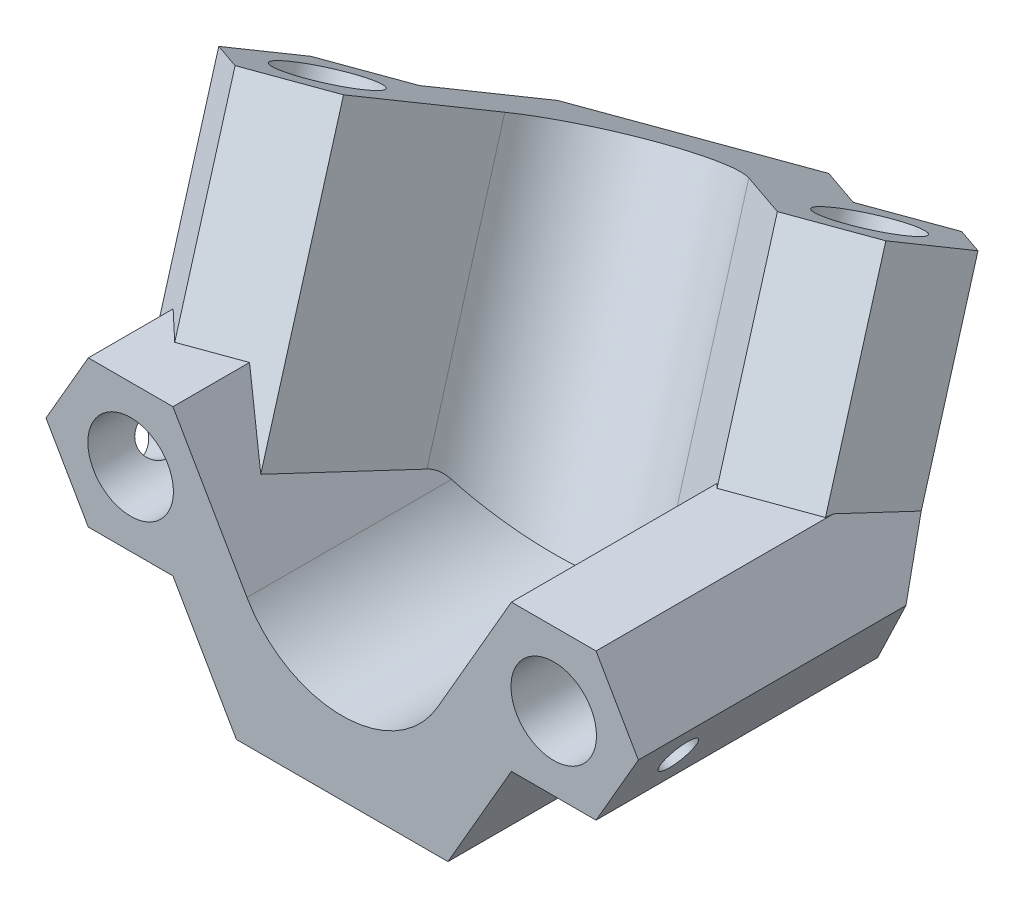
SolidWorks part; units mm, degrees
ref_plane "Front Plane" through (0, 0, 0) normal (0, 0, 1) x (1, 0, 0)
ref_plane "Top Plane" through (0, 0, 0) normal (0, 1, 0) x (1, 0, 0)
ref_plane "Right Plane" through (0, 0, 0) normal (1, 0, 0) x (0, 0, -1)
sketch "Sketch1" plane through (0, 0, 0) normal (0, 1, 0) x (1, 0, 0)
  line L0 (0, 0) -> (0, -10) construction
  line L1 (0, 0) -> (-3.4202, 9.3969) construction
  dimension "D1" = 10
  dimension "D2" = 160
  dimension "D3" = 10
ref_plane "Plane1" through (0, 0, 0) normal (0.9397, 0, -0.342) x (-0.342, 0, -0.9397)
sketch "Sketch2" plane through (0, 0, 0) normal (0.9397, 0, -0.342) x (-0.342, 0, -0.9397)
  line L0 (0, 0) -> (10, 0) construction
  line L1 (0, 0) -> (10, 0) construction
  line L2 (10, 0) -> (10, 17.3205) construction
  line L3 (10, 17.3205) -> (0, 0) construction
  dimension "D1" = 60
  dimension "D2" = 10
sketch "Sketch3" plane through (0, 0, 0) normal (0, 0, 1) x (1, 0, 0)
  line L0 (0, 15) -> (0, -15) construction
  line L1 (13.8564, 6) -> (8.6603, 15) construction
  line L2 (8.6603, 15) -> (0, 15) construction
  line L3 (-8.6603, 15) -> (-13.8564, 6) construction
  line L4 (-13.8564, -6) -> (-8.6603, -15)
  line L5 (-8.6603, -15) -> (8.6603, -15)
  line L6 (8.6603, -15) -> (13.8564, -6)
  line L7 (0, 0) -> (17.3205, 0) construction
  line L8 (13.8564, 6) -> (12.1244, 3) construction
  line L9 (24.2487, 0) -> (20.7846, 6)
  line L10 (20.7846, 6) -> (13.8564, 6)
  line L11 (12.1244, 3) -> (7.7942, -4.5) construction
  line L12 (12.1244, -3) -> (13.8564, -6) construction
  line L13 (13.8564, -6) -> (20.7846, -6)
  line L14 (20.7846, -6) -> (24.2487, 0)
  line L15 (10.3923, 0) -> (12.1244, -3) construction
  line L16 (13.8564, -6) -> (14.3205, -5.1962) construction
  line L17 (15.5705, -3.0311) -> (17.3205, 0) construction
  line L18 (14.3205, -5.1962) -> (15.5705, -3.0311) construction
  line L19 (17.3205, 0) -> (15.5705, 3.0311) construction
  line L20 (15.5705, 3.0311) -> (14.3205, 5.1962) construction
  line L21 (14.3205, 5.1962) -> (13.8564, 6) construction
  line L22 (-13.8564, -6) -> (-20.7846, -6)
  line L23 (-20.7846, -6) -> (-24.2487, 0)
  line L24 (-24.2487, 0) -> (-20.7846, 6)
  line L25 (-20.7846, 6) -> (-13.8564, 6)
  line L26 (-13.8564, 6) -> (-15.5705, 3.0311) construction
  line L27 (-15.5705, 3.0311) -> (-17.3205, 0) construction
  line L28 (-17.3205, 0) -> (-15.5705, -3.0311) construction
  line L29 (-15.5705, -3.0311) -> (-13.8564, -6) construction
  line L30 (-17.3205, 6) -> (-17.3205, -6) construction
  line L31 (-7.7942, -4.5) -> (-13.8564, 6)
  line L32 (7.7942, -4.5) -> (13.8564, 6)
  line L33 (-10.3923, 0) -> (-7.7942, -4.5) construction
  line L34 (0, 15) -> (-8.6603, 15) construction
  line L35 (7.7942, -4.5) -> (10.3923, 0) construction
  line L36 (10.3923, 0) -> (7.7942, -4.5) construction
  circle A0 centre (0, 0) radius 15 construction
  circle A1 centre (17.3205, 0) radius 3.5
  circle A2 centre (17.3205, 0) radius 6 construction
  circle A3 centre (-17.3205, 0) radius 3.5
  arc A4 (-7.7942, -4.5) -> (7.7942, -4.5) centre (0, 0) ccw
  arc A5 (0, 9) -> (-7.7942, -4.5) centre (0, 0) ccw construction
  arc A6 (7.7942, -4.5) -> (0, 9) centre (0, 0) ccw construction
  dimension "D2" = 7
  dimension "D4" = 18
  dimension "D1" = 30
  dimension "D3" = 12
extrude "Boss-Extrude1" add sketch "Sketch3" along normal blind 15
ref_plane "Plane2" through (-3.4202, 17.3205, -9.3969) normal (0.171, -0.866, 0.4698) x (-0.9849, -0.1641, 0.056)
sketch "Sketch25" plane through (0, 0, 0) normal (0, 0, -1) x (-1, 0, 0)
  line L0 (-7.7942, -4.5) -> (-13.8564, 6)
  line L1 (-13.8564, 6) -> (-20.7846, 6)
  line L2 (-20.7846, 6) -> (-24.2487, 0)
  line L3 (-24.2487, 0) -> (-20.7846, -6)
  line L4 (-20.7846, -6) -> (-13.8564, -6)
  line L5 (-13.8564, -6) -> (-8.6603, -15)
  line L6 (-8.6603, -15) -> (8.6603, -15)
  line L7 (8.6603, -15) -> (13.8564, -6)
  line L8 (13.8564, -6) -> (20.7846, -6)
  line L9 (20.7846, -6) -> (24.2487, 0)
  line L10 (24.2487, 0) -> (20.7846, 6)
  line L11 (20.7846, 6) -> (13.8564, 6)
  line L12 (13.8564, 6) -> (7.7942, -4.5)
  arc A0 (-7.7942, -4.5) -> (7.7942, -4.5) centre (0, 0) ccw
  arc A1 (-7.7942, -4.5) -> (7.7942, -4.5) centre (0, 0) ccw construction
  arc A2 (7.7942, -4.5) -> (-7.7942, -4.5) centre (0, 0) ccw construction
sketch "Sketch11" plane through (-3.4202, 17.3205, -9.3969) normal (0.171, -0.866, 0.4698) x (-0.9849, -0.1641, 0.056)
  line L0 (-4.9224, -14.1693) -> (4.9224, 14.1693) construction
  line L7 (13.1031, 11.3274) -> (-3.2583, 17.0113)
  line L20 (-3.2583, 17.0113) -> (-11.1201, 10.2148)
  line L21 (-15.058, -1.1206) -> (-13.1031, -11.3274) construction
  line L22 (-4.9224, -14.1693) -> (3.2583, -17.0113) construction
  line L23 (3.2583, -17.0113) -> (11.1201, -10.2148) construction
  line L24 (16.3613, -5.6839) -> (15.7029, -2.2464) construction
  line L25 (2.8419, 8.1807) -> (0, 0) construction
  line L26 (-16.3613, 5.6839) -> (16.3613, -5.6839) construction
  line L27 (15.058, 1.1206) -> (12.4374, -1.1449) construction
  line L28 (-11.1201, 10.2148) -> (-17.6647, 12.4884)
  line L35 (-17.6647, 12.4884) -> (-22.9059, 7.9574)
  line L42 (-22.9059, 7.9574) -> (-21.6026, 1.1529)
  line L43 (-21.6026, 1.1529) -> (-15.058, -1.1206)
  line L44 (-15.058, -1.1206) -> (-5.8859, 6.8085)
  line L45 (-8.8393, -1.6931) -> (-10.4685, 6.8126) construction
  line L46 (22.9059, -7.9574) -> (21.6026, -1.1529)
  line L47 (21.6026, -1.1529) -> (15.058, 1.1206)
  line L48 (5.8859, -6.8085) -> (9.8168, -3.4103) construction
  line L49 (8.8393, 1.6931) -> (11.1201, -10.2148)
  line L50 (11.1201, -10.2148) -> (17.6647, -12.4884)
  line L51 (17.6647, -12.4884) -> (22.9059, -7.9574)
  line L52 (12.4374, -1.1449) -> (5.8859, -6.8085) construction
  line L53 (9.8168, -3.4103) -> (8.8393, 1.6931) construction
  line L54 (15.2326, 0.209) -> (15.058, 1.1206) construction
  line L55 (15.058, 1.1206) -> (13.1031, 11.3274)
  line L56 (15.7029, -2.2464) -> (15.2326, 0.209) construction
  line L57 (13.7136, -7.9728) -> (16.3613, -5.6839) construction
  line L58 (11.8223, -9.6078) -> (13.7136, -7.9728) construction
  line L59 (11.1201, -10.2148) -> (11.8223, -9.6078) construction
  line L60 (-10.4685, 6.8126) -> (-11.1201, 10.2148) construction
  line L61 (-11.8223, 9.6078) -> (-13.7136, 7.9728) construction
  line L62 (-13.7136, 7.9728) -> (-16.3613, 5.6839) construction
  line L63 (-16.3613, 5.6839) -> (-15.7029, 2.2464) construction
  line L64 (-11.1201, 10.2148) -> (-11.8223, 9.6078) construction
  line L65 (-15.7029, 2.2464) -> (-15.2326, -0.209) construction
  line L66 (-15.2326, -0.209) -> (-15.058, -1.1206) construction
  line L67 (-5.8859, 6.8085) -> (-9.8168, 3.4103) construction
  line L68 (-9.8168, 3.4103) -> (-8.8393, -1.6931) construction
  line L69 (-13.1031, -11.3274) -> (-4.9224, -14.1693) construction
  circle A0 centre (0, 0) radius 15 construction
  circle A2 centre (-16.3613, 5.6839) radius 6 construction
  circle A4 centre (-16.3613, 5.6839) radius 3.5
  circle A5 centre (16.3613, -5.6839) radius 6 construction
  circle A6 centre (16.3613, -5.6839) radius 3.5
  arc A7 (8.8393, 1.6931) -> (-5.8859, 6.8085) centre (0, 0) ccw
  arc A8 (-2.9534, -8.5016) -> (8.8393, 1.6931) centre (0, 0) ccw construction
  arc A9 (-5.8859, 6.8085) -> (-2.9534, -8.5016) centre (0, 0) ccw construction
  dimension "D2" = 12
  dimension "D4" = 12
  dimension "D3" = 7
  dimension "D5" = 7
  dimension "D6" = 18
  dimension "D1" = 30
extrude "Boss-Extrude6" add sketch "Sketch11" along normal up to surface (33.8564 mm away) up to face at (0, -15, 7.5)
sketch "Sketch22" plane through (0, 0, 15) normal (0, 0, 1) x (1, 0, 0)
  line L0 (8.6603, -15) -> (-7.1843, -15)
  line L1 (-9.2861, -6.9129) -> (-7.1843, -15) construction
  circle A0 centre (-17.3205, 0) radius 3.5
  arc A1 (-15.7099, -3.1074) -> (-17.8449, 3.4605) centre (-17.3205, 0) ccw construction
  circle A2 centre (17.3205, 0) radius 3.5
  circle A3 centre (17.3205, 0) radius 3.5 construction
  circle A4 centre (0, 0) radius 9
  arc A5 (-7.7942, -4.5) -> (7.7942, -4.5) centre (0, 0) ccw construction
  point P18 (0, 0)
  point P20 (-7.1843, -15)
  arc M23 (7.7942, -4.5) -> (-7.7942, -4.5) centre (0, 0) cw
extrude "Cut-Extrude5" cut sketch "Sketch22" against normal up to surface (15 mm away) contours A4 M23 | A0 | A2 region at (0, 0, 15) up to face at (-19.4628, -1.9467, 0)
sketch "Sketch23" plane through (0, 0, 0) normal (0, 1, 0) x (1, 0, 0)
  line L0 (24.2487, -15) -> (24.2487, 0) construction
  line L1 (-24.2487, -15) -> (24.2487, -15)
  line L2 (-24.2487, -15) -> (-24.2487, -21.7571)
  line L3 (-24.2487, -21.7571) -> (24.2487, -21.7571)
  line L4 (24.2487, -15) -> (24.2487, -21.7571)
extrude "Cut-Extrude6" cut sketch "Sketch23" against normal through all both and the other way through all
sketch "Sketch24" plane through (0, 0, 15) normal (0, 0, 1) x (1, 0, 0)
  line L0 (-24.2487, 0) -> (-20.7846, -6)
  line L1 (-20.7846, -6) -> (-13.8564, -6)
  line L2 (-13.8564, -6) -> (-8.6603, -15)
  line L3 (-8.6603, -15) -> (-19.6596, -15)
  line L4 (-19.6596, -15) -> (-24.2487, 0)
  line L5 (8.6603, -15) -> (13.8564, -6)
  line L6 (13.8564, -6) -> (20.7846, -6)
  line L7 (20.7846, -6) -> (24.2487, 0)
  line L8 (24.2487, 0) -> (25.7483, -15)
  line L9 (25.7483, -15) -> (8.6603, -15)
  point P14 (0, 0)
extrude "Cut-Extrude7" cut sketch "Sketch24" against normal through all both and the other way through all
extrude "Boss-Extrude7" add sketch "Sketch25" along normal up to surface (18.5042 mm away) up to face at (-6.3157, -3.7874, -13.8064)
sketch "Sketch26" plane through (-3.4202, 17.3205, -9.3969) normal (-0.171, 0.866, -0.4698) x (0.9853, 0.1503, -0.0815)
  line L0 (-12.769, 11.7026) -> (-15.0192, 1.5568)
  line L1 (-15.0192, 1.5568) -> (-24.01, -1.2771)
  line L2 (-25.1148, -13.1846) -> (-23.1081, 8.4437) construction
  line L3 (-24.01, -1.2771) -> (-23.1081, 8.4437)
  line L4 (-23.1081, 8.4437) -> (-12.769, 11.7026)
  line L5 (3.7502, 16.9096) -> (11.4117, 9.8881)
  line L6 (11.4117, 9.8881) -> (18.0194, 11.9709)
  line L7 (18.0194, 11.9709) -> (24.4549, 6.0728)
  line L8 (22.6683, -13.1846) -> (26.1144, 23.959) construction
  line L9 (24.4549, 6.0728) -> (26.1144, 23.959)
  line L10 (26.1144, 23.959) -> (3.7502, 16.9096)
extrude "Cut-Extrude8" cut sketch "Sketch26" against normal through all both and the other way through all
sketch "Sketch27" plane through (-18.1865, -10.5, 0) normal (-0.866, -0.5, 0) x (0, 0, 1)
  line L0 (15, 8.6603) -> (2.6658, 8.6603) construction
  line L1 (15, 12.1244) -> (15, 5.1962) construction
  line L2 (1.453, 12.1244) -> (3.8786, 5.1962) construction
  line L3 (10, 12.1244) -> (10, 5.1962) construction
  line L4 (15, 12.1244) -> (1.453, 12.1244) construction
  line L5 (15, 5.1962) -> (3.8786, 5.1962) construction
  circle A0 centre (10, 8.6603) radius 1.5
  dimension "D1" = 3
  dimension "D2" = 5
extrude "Cut-Extrude9" cut sketch "Sketch27" against normal up to surface and the other way through all up to face at (-17.3205, 0, 0.7154)
sketch "Sketch28" plane through (18.1865, -10.5, 0) normal (0.866, -0.5, 0) x (0, 0, -1)
  line L0 (-15, 8.6603) -> (7.4822, 8.6603) construction
  line L1 (-15, 5.1962) -> (-15, 12.1244) construction
  line L2 (8.0554, 5.1962) -> (6.909, 12.1244) construction
  circle A0 centre (-10, 8.6603) radius 1.5
  dimension "D1" = 3
  dimension "D2" = 5
extrude "Cut-Extrude10" cut sketch "Sketch28" against normal up to surface (2.8377 mm away) up to face at (20.8205, 0, 0)
sketch "Sketch29" plane through (-20.1998, -5.25, -2.3247) normal (-0.9619, -0.25, -0.1107) x (-0.1071, -0.0278, 0.9939)
  line L0 (-1.8237, 21.7181) -> (5.4703, 8.1224) construction
  line L1 (1.2289, 23.3557) -> (-4.8762, 20.0804) construction
  line L2 (1.2869, 8.5925) -> (9.6536, 7.6523) construction
  circle A0 centre (0.5401, 17.3121) radius 1.5
  dimension "D1" = 3
  dimension "D2" = 5
extrude "Cut-Extrude11" cut sketch "Sketch29" against normal up to surface (2.5726 mm away) contours A0 up to face at (-19.6962, 15.6515, -6.5494)
sketch "Sketch30" plane through (13.9797, -5.25, -14.765) normal (0.6657, -0.25, -0.7031) x (-0.7462, -0.223, -0.6272)
  line L0 (-3.8464, 21.4524) -> (-9.4928, -2.5305) construction
  line L1 (-0.4745, 20.6585) -> (-7.2183, 22.2463) construction
  line L2 (-9.1192, -2.9545) -> (-13.7614, 2.3146) construction
  circle A0 centre (-4.9923, 16.5855) radius 1.5
  dimension "D1" = 3
  dimension "D2" = 5
extrude "Cut-Extrude12" cut sketch "Sketch30" against normal up to surface (2.7674 mm away) up to face at (12.8558, 15.6515, -18.3973)
sketch "Sketch31" plane through (-4.443, -7.5, -12.207) normal (-0.2962, -0.5, -0.8138) x (-0.9551, 0.1551, 0.2524)
  line L0 (3.5809, 19.6768) -> (-1.5506, -8.5203) construction
  line L1 (12.1012, 18.1262) -> (-4.9394, 21.2274) construction
  line L2 (-10.0709, -6.9697) -> (4.4154, -9.606) construction
  line L3 (-4.0102, -8.0727) -> (-2.5778, -0.202)
  line L4 (-2.5778, -0.202) -> (2.3414, -1.0972)
  line L5 (2.3414, -1.0972) -> (0.909, -8.9679)
  line L6 (0.909, -8.9679) -> (-4.0102, -8.0727)
  point P8 (-0.1182, -0.6496)
  dimension "D1" = 5
  dimension "D2" = 8
extrude "Boss-Extrude8" add sketch "Sketch31" along normal blind 10
sketch "Sketch32" plane through (2.3492, 0, -0.8551) normal (0.9397, 0, -0.342) x (-0.342, 0, -0.9397)
  line L0 (19.3205, -16.5359) -> (10.6603, -11.5359) construction
  line L3 (21.3205, -13.0718) -> (17.3205, -20) construction
  line L4 (8.6603, -15) -> (22.9904, 9.8205) construction
  circle A0 centre (17.1554, -15.2859) radius 1.5
  point P8 (15.3119, -14.2215)
  point P9 (10.7051, -11.4582)
  dimension "D1" = 3
  dimension "D2" = 2.5
extrude "Cut-Extrude13" cut sketch "Sketch32" against normal through all
fillet "Fillet1" radius 3 1 edges at (-7.292, -13.0718, -20.0347) type face fillet first side face at (-6.608, -16.5359, -18.1553) second side face at (-5.8111, -10.5718, -15.9657)
fillet "Fillet2" radius 3 1 edges at (-5.924, -20, -16.276) type face fillet first side face at (-6.3515, -17.8349, -17.4506) second side face at (-4.443, -17.5, -12.207)
sketch "Sketch33" plane through (-4.443, -7.5, -12.207) normal (-0.2962, -0.5, -0.8138) x (-0.9551, 0.1551, 0.2524)
  line L0 (-1.5506, -8.5203) -> (20.9683, 115.2197) construction
  line L1 (-4.0102, -8.0727) -> (0.909, -8.9679) construction
  line L2 (12.1012, 18.1262) -> (-4.9394, 21.2274) construction
